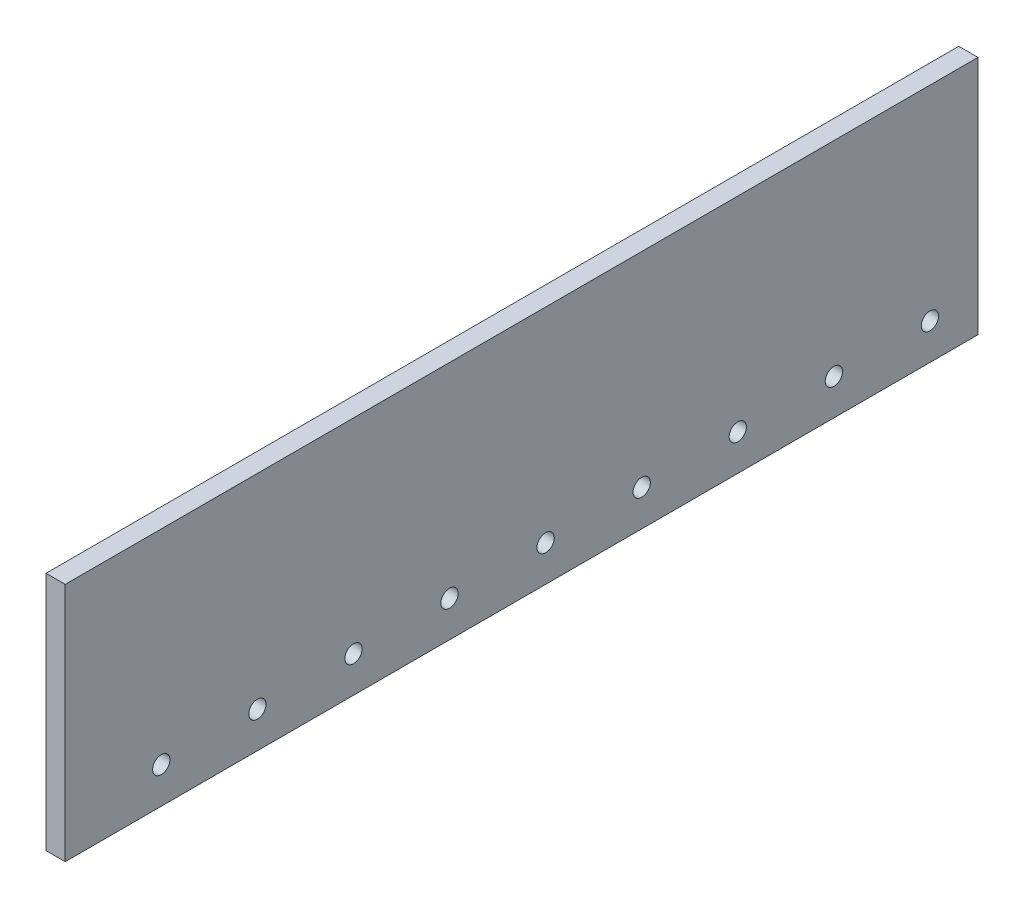
SolidWorks part; units mm, degrees
ref_plane "Front Plane" through (0, 0, 0) normal (0, 0, 1) x (1, 0, 0)
ref_plane "Top Plane" through (0, 0, 0) normal (0, 1, 0) x (1, 0, 0)
ref_plane "Right Plane" through (0, 0, 0) normal (1, 0, 0) x (0, 0, -1)
sketch "Sketch2" plane through (0, 0, 0) normal (1, 0, 0) x (0, 0, -1)
  line L0 (-84.2593, 50.216) -> (105.7407, 50.216)
  line L1 (-84.2593, 50.216) -> (-84.2593, 0.216)
  line L2 (105.7407, 50.216) -> (105.7407, 0.216)
  line L3 (-84.2593, 0.216) -> (105.7407, 0.216)
  circle A0 centre (-64.2593, 7.716) radius 1.8
  circle A1 centre (-44.2593, 7.716) radius 1.8
  circle A2 centre (-24.2593, 7.716) radius 1.8
  circle A3 centre (-4.2593, 7.716) radius 1.8
  circle A4 centre (15.7407, 7.716) radius 1.8
  circle A5 centre (35.7407, 7.716) radius 1.8
  circle A6 centre (55.7407, 7.716) radius 1.8
  circle A7 centre (75.7407, 7.716) radius 1.8
  circle A8 centre (95.7407, 7.716) radius 1.8
  dimension "D3" = 7.5
  dimension "D1" = 50
  dimension "D2" = 190
  dimension "D4" = 20
  dimension "D5" = 9
extrude "Boss-Extrude1" add sketch "Sketch2" along normal blind 4
